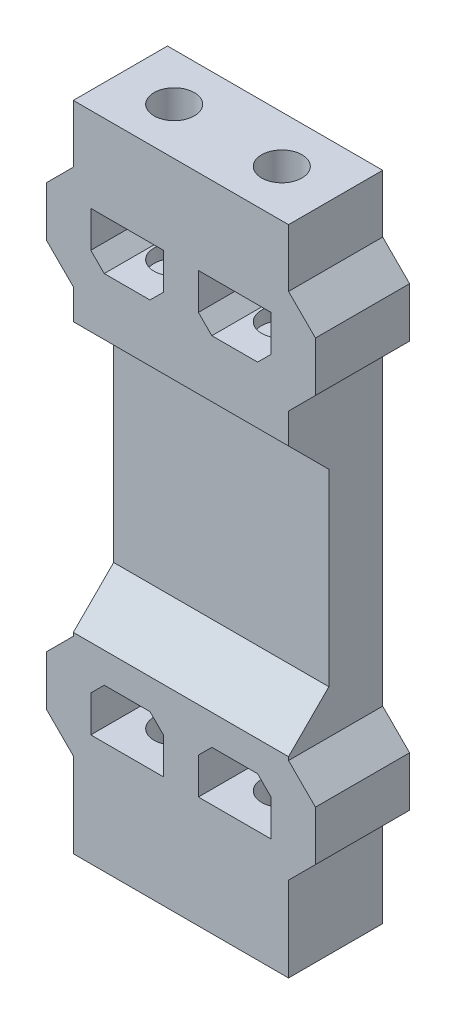
SolidWorks part; units mm, degrees
material "PETG"
ref_plane "Front Plane" through (0, 0, 0) normal (0, 0, 1) x (1, 0, 0)
ref_plane "Top Plane" through (0, 0, 0) normal (0, 1, 0) x (1, 0, 0)
ref_plane "Right Plane" through (0, 0, 0) normal (1, 0, 0) x (0, 0, -1)
sketch "Sketch1" plane through (0, 0, 0) normal (0, 0, 1) x (1, 0, 0)
  line L1 (-8, -24.25) -> (8, -24.25)
  line L2 (-8, -24.25) -> (-8, 24.25)
  line L3 (-8, 24.25) -> (8, 24.25)
  line L4 (8, -24.25) -> (8, 24.25)
  line L5 (-8, -24.25) -> (8, 24.25) construction
  line L6 (-8, 24.25) -> (8, -24.25) construction
  point P0 (0, 0)
  dimension "D1" = 16
  dimension "D2" = 48.5
extrude "Boss-Extrude1" add sketch "Sketch1" along normal blind 7
sketch "Sketch2" plane through (0, 0, 7) normal (0, 0, 1) x (1, 0, 0)
  line L0 (0, 33.8506) -> (0, -34.745) construction
  line L2 (-6.7, 17.95) -> (-1.3, 17.95)
  line L3 (-6.7, 17.95) -> (-6.7, 14.25)
  line L4 (-6.7, 14.25) -> (-1.3, 14.25)
  line L5 (-1.3, 17.95) -> (-1.3, 14.25)
  line L6 (-6.7, 17.95) -> (-1.3, 14.25) construction
  line L7 (-6.7, 14.25) -> (-1.3, 17.95) construction
  line L8 (6.7, 14.25) -> (1.3, 17.95) construction
  line L9 (6.7, 17.95) -> (1.3, 14.25) construction
  line L10 (1.3, 17.95) -> (1.3, 14.25)
  line L11 (6.7, 14.25) -> (1.3, 14.25)
  line L12 (6.7, 17.95) -> (6.7, 14.25)
  line L13 (6.7, 17.95) -> (1.3, 17.95)
  line L14 (-18.9875, 1) -> (27.0845, 1) construction
  line L15 (6.7, -15.95) -> (1.3, -12.25) construction
  line L16 (6.7, -12.25) -> (1.3, -15.95) construction
  line L17 (-6.7, -12.25) -> (-1.3, -15.95) construction
  line L18 (-6.7, -15.95) -> (-1.3, -12.25) construction
  line L19 (6.7, -15.95) -> (1.3, -15.95)
  line L20 (6.7, -15.95) -> (6.7, -12.25)
  line L21 (6.7, -12.25) -> (1.3, -12.25)
  line L22 (1.3, -15.95) -> (1.3, -12.25)
  line L23 (-1.3, -15.95) -> (-1.3, -12.25)
  line L24 (-6.7, -12.25) -> (-1.3, -12.25)
  line L25 (-6.7, -15.95) -> (-6.7, -12.25)
  line L26 (-6.7, -15.95) -> (-1.3, -15.95)
  line L27 (8, 24.25) -> (-8, 24.25) construction
  point P3 (-4, 16.1)
  point P14 (4, 16.1)
  point P25 (4, -14.1)
  point P26 (-4, -14.1)
  dimension "D1" = 5.4
  dimension "D2" = 3.7
  dimension "D3" = 10
  dimension "D4" = 1.3
  dimension "D5" = 1
extrude "Cut-Extrude1" cut sketch "Sketch2" against normal through all
sketch "Sketch3" plane through (0, 24.25, 0) normal (0, 1, 0) x (1, 0, 0)
  line L0 (-6.7, 0) -> (-1.3, 0) construction
  line L1 (-1.3, 0) -> (-1.3, -7) construction
  line L2 (-6.7, -7) -> (-1.3, -7) construction
  line L3 (-6.7, 0) -> (-6.7, -7) construction
  line L4 (8, 0) -> (-8, 0)
  line L5 (-8, 0) -> (-8, -7)
  line L6 (-8, -7) -> (8, -7)
  line L7 (8, -7) -> (8, 0)
  line L8 (8, 0) -> (-8, 0)
  line L9 (-8, 0) -> (-8, -7)
  line L10 (-8, -7) -> (8, -7)
  line L11 (8, -7) -> (8, 0)
  line L12 (1.3, -7) -> (6.7, -7) construction
  line L13 (6.7, 0) -> (6.7, -7) construction
  line L14 (1.3, 0) -> (6.7, 0) construction
  line L15 (1.3, 0) -> (1.3, -7) construction
  line L16 (-6.7, 0) -> (-1.3, 0) construction
  line L17 (-1.3, 0) -> (-1.3, -7) construction
  line L18 (-6.7, -7) -> (-1.3, -7) construction
  line L19 (-6.7, 0) -> (-6.7, -7) construction
  line L20 (1.3, -7) -> (6.7, -7) construction
  line L21 (6.7, 0) -> (6.7, -7) construction
  line L22 (1.3, 0) -> (6.7, 0) construction
  line L23 (1.3, 0) -> (1.3, -7) construction
  line L25 (6.7, 0) -> (1.3, 0) construction
  line L26 (6.7, 0) -> (6.7, -7) construction
  line L27 (6.7, -7) -> (1.3, -7) construction
  line L28 (1.3, 0) -> (1.3, -7) construction
  line L29 (6.7, 0) -> (1.3, -7) construction
  line L30 (6.7, -7) -> (1.3, 0) construction
  line L31 (-1.3, 0) -> (-6.7, 0) construction
  line L32 (-1.3, 0) -> (-1.3, -7) construction
  line L33 (-1.3, -7) -> (-6.7, -7) construction
  line L34 (-6.7, 0) -> (-6.7, -7) construction
  line L35 (-1.3, 0) -> (-6.7, -7) construction
  line L36 (-1.3, -7) -> (-6.7, 0) construction
  circle A0 centre (4, -3.5) radius 1.5
  circle A1 centre (-4, -3.5) radius 1.5
  point P6 (4, -3.5)
  point P17 (-4, -3.5)
  dimension "D2" = 3
  dimension "D1" = 0
extrude "Cut-Extrude2" cut sketch "Sketch3" against normal blind 11 flip side to cut
mirror "Mirror1" about plane through (0, 0, 0) normal (0, 1, 0) of "Cut-Extrude2"
sketch "Sketch4" plane through (0, 0, 7) normal (0, 0, 1) x (1, 0, 0)
  line L0 (8, -24.25) -> (8, 24.25) construction
  line L1 (-8, -10) -> (8, -10)
  line L2 (-8, -10) -> (-8, 10)
  line L3 (-8, 10) -> (8, 10)
  line L4 (8, -10) -> (8, 10)
  line L5 (-8, -10) -> (8, 10) construction
  line L6 (-8, 10) -> (8, -10) construction
  point P0 (0, 0)
  dimension "D1" = 20
extrude "Cut-Extrude3" cut sketch "Sketch4" against normal blind 3
chamfer "Chamfer1" distance 3 angle 45 2 edges at (0, -10, 4) (0, 10, 4)
sketch "Sketch5" plane through (0, 0, 0) normal (0, 0, -1) x (-1, 0, 0)
  line L0 (8, 24.25) -> (8, 10) construction
  line L1 (8, 19.95) -> (10, 19.95)
  line L2 (8, 19.95) -> (8, 12.25)
  line L3 (8, 12.25) -> (10, 12.25)
  line L4 (10, 19.95) -> (10, 12.25)
  line L5 (1.3, 17.95) -> (6.7, 17.95) construction
  line L6 (6.7, 14.25) -> (1.3, 14.25) construction
  line L7 (0, 0) -> (0, 50000) construction
  line L8 (0, 1) -> (50000, 1) construction
  line L9 (-10, 19.95) -> (-10, 12.25)
  line L10 (-8, 12.25) -> (-10, 12.25)
  line L11 (-8, 19.95) -> (-8, 12.25)
  line L12 (-8, 19.95) -> (-10, 19.95)
  line L13 (-8, -17.95) -> (-10, -17.95)
  line L14 (-8, -17.95) -> (-8, -10.25)
  line L15 (-8, -10.25) -> (-10, -10.25)
  line L16 (-10, -17.95) -> (-10, -10.25)
  line L17 (10, -17.95) -> (10, -10.25)
  line L18 (8, -10.25) -> (10, -10.25)
  line L19 (8, -17.95) -> (8, -10.25)
  line L20 (8, -17.95) -> (10, -17.95)
  dimension "D1" = 2
  dimension "D2" = 2
  dimension "D3" = 2
  dimension "D4" = 1
extrude "Boss-Extrude2" add sketch "Sketch5" against normal up to surface (7 mm away) up to face at (0, 17.125, 7)
chamfer "Chamfer2" distance 2 angle 45 8 edges at (-10, -17.95, 3.5) (-10, -10.25, 3.5) (10, -17.95, 3.5) (10, -10.25, 3.5) (10, 12.25, 3.5) (10, 19.95, 3.5) (-10, 12.25, 3.5) (-10, 19.95, 3.5)
chamfer "Chamfer3" distance 1 angle 45 8 edges at (6.7, -12.25, 3.5) (-1.3, -12.25, 3.5) (1.3, -12.25, 3.5) (-6.7, -12.25, 3.5) (6.7, 14.25, 3.5) (1.3, 14.25, 3.5) (-1.3, 14.25, 3.5) (-6.7, 14.25, 3.5)
